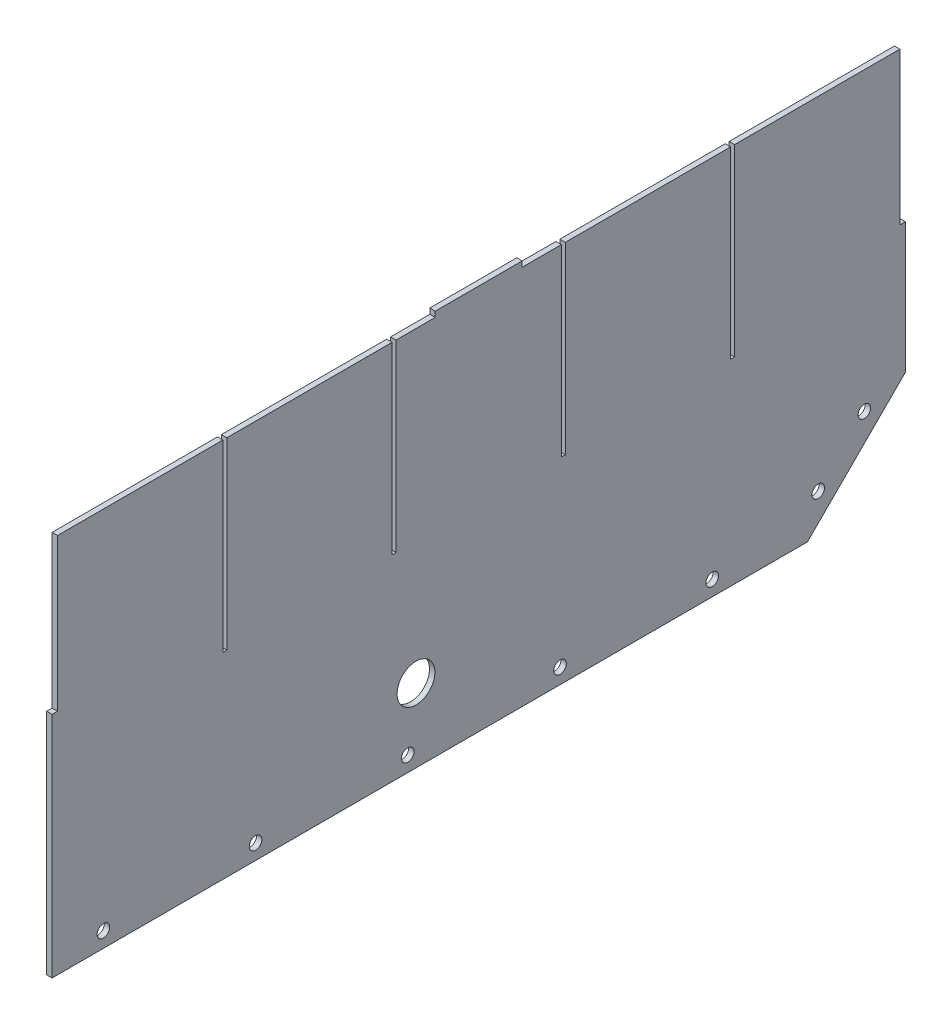
SolidWorks part; units mm, degrees
material "6061-T6 (SS)"
ref_plane "X-Y Datum" through (0, 0, 0) normal (0, 0, 1) x (1, 0, 0)
ref_plane "X-Z Datum" through (0, 0, 0) normal (0, 1, 0) x (1, 0, 0)
ref_plane "Y-Z Datum" through (0, 0, 0) normal (1, 0, 0) x (0, 0, -1)
sketch "Sketch1" plane through (0, 0, 0) normal (1, 0, 0) x (0, 0, -1)
  line L1 (-249.174, 82.55) -> (249.174, 82.55)
  line L2 (-249.174, 82.55) -> (-249.174, -82.55)
  line L3 (-249.174, -82.55) -> (249.174, -82.55)
  line L4 (249.174, 82.55) -> (249.174, -82.55)
  line L5 (-249.174, 82.55) -> (249.174, -82.55) construction
  line L6 (-249.174, -82.55) -> (249.174, 82.55) construction
  point P0 (0, 0)
  dimension "D1" = 165.1
  dimension "D2" = 498.348
extrude "Boss-Extrude1" add sketch "Sketch1" along normal mid plane 3.175
sketch "Sketch2" plane through (1.5875, 0, 0) normal (1, 0, 0) x (0, 0, -1)
  line L2 (249.174, -82.55) -> (192.024, -139.7)
  line L5 (-249.174, -82.55) -> (249.174, -82.55) construction
  line L6 (-249.174, -82.55) -> (249.174, -82.55)
  line L8 (192.024, -139.7) -> (-249.174, -139.7)
  line L9 (-249.174, -139.7) -> (-249.174, -82.55)
  line L11 (-249.174, 82.55) -> (-249.174, -82.55) construction
  line L12 (249.174, -82.55) -> (249.174, 82.55) construction
  line M10 (-249.174, -82.55) -> (249.174, -82.55)
  dimension "D1" = 45
  dimension "D5" = 57.15
extrude "Boss-Extrude2" add sketch "Sketch2" against normal blind 3.175 contours L2 M10 region at (1.5875, -110.5456, 13.9978)
sketch "Sketch3" plane through (-1.5875, 0, 0) normal (-1, 0, 0) x (0, 0, 1)
  line L0 (219.202, -139.7) -> (219.202, -130.81)
  line L1 (-192.024, -139.7) -> (249.174, -139.7) construction
  line L2 (219.202, -130.81) -> (249.174, -130.81)
  line L3 (249.174, 82.55) -> (249.174, -139.7) construction
  circle A0 centre (219.202, -130.81) radius 3.675
  dimension "D1" = 7.35
extrude "Cut-Extrude1" cut sketch "Sketch3" against normal through all contours L0 A0 L2 | L2 A0 L0 region at (-1.5875, -130.2901, 218.6821) region at (-1.5875, -132.3697, 220.7617)
pattern_linear "LPattern1" count 5 spacing 88.9 along (0, 0, -1) of "Cut-Extrude1"
sketch "Sketch4" plane through (-1.5875, 0, 0) normal (-1, 0, 0) x (0, 0, 1)
  line L0 (-206.3924, -125.3316) -> (-198.3102, -117.2494)
  line L1 (-249.174, -82.55) -> (-192.024, -139.7) construction
  line L2 (-192.024, -139.7) -> (-183.9418, -131.6178)
  line L3 (-183.9418, -131.6178) -> (-198.3102, -117.2494)
  circle A0 centre (-198.3102, -117.2494) radius 3.675
extrude "Cut-Extrude2" cut sketch "Sketch4" against normal through all and the other way through all contours L3 A0 L0 | L0 A0 L3 region at (-1.5875, -116.5141, -198.3102) region at (-1.5875, -119.4551, -198.3102)
pattern_linear "LPattern2" count 2 spacing 38.1 along (0, 0.7071, -0.7071) of "Cut-Extrude2"
sketch "Sketch5" plane through (1.5875, 0, 0) normal (1, 0, 0) x (0, 0, -1)
  line L1 (249.174, 82.55) -> (245.999, 82.55)
  line L2 (249.174, 82.55) -> (249.174, -6.35)
  line L3 (249.174, -6.35) -> (245.999, -6.35)
  line L4 (245.999, 82.55) -> (245.999, -6.35)
  line L5 (-249.174, 82.55) -> (-245.999, 82.55)
  line L6 (-249.174, 82.55) -> (-249.174, -6.35)
  line L7 (-249.174, -6.35) -> (-245.999, -6.35)
  line L8 (-245.999, 82.55) -> (-245.999, -6.35)
  dimension "D1" = 3.175
  dimension "D2" = 88.9
  dimension "D3" = 3.175
  dimension "D4" = 88.9
extrude "Cut-Extrude3" cut sketch "Sketch5" against normal through all
sketch "Sketch6" plane through (1.5875, 0, 0) normal (1, 0, 0) x (0, 0, -1)
  line L0 (122.174, 82.55) -> (249.174, 82.55) construction
  line L1 (149.4282, -24.892) -> (149.4282, 82.55) construction
  line L2 (122.174, 82.55) -> (249.174, 82.55)
  line L3 (149.4282, -24.892) -> (149.4282, 82.55)
  line L5 (149.4282, 82.55) -> (147.1422, 82.55)
  line L6 (149.4282, 82.55) -> (149.4282, -24.892)
  line L7 (149.4282, -24.892) -> (147.1422, -24.892)
  line L8 (147.1422, 82.55) -> (147.1422, -24.892)
  dimension "D1" = 2.286
  dimension "D2" = 107.442
extrude "Cut-Extrude4" cut sketch "Sketch6" against normal through all contours L2 L8 L7 L3 region at (1.5875, 28.829, -148.2852)
pattern_linear "LPattern3" count 4 spacing 98.8568 along (0, 0, 1) of "Cut-Extrude4"
sketch "Sketch8" plane through (1.5875, 0, 0) normal (1, 0, 0) x (0, 0, -1)
  line L0 (122.174, 85.725) -> (25.4, 85.725) construction
  line L1 (25.4, 82.55) -> (-25.4, 82.55)
  line L2 (25.4, 82.55) -> (25.4, 85.725)
  line L3 (25.4, 85.725) -> (-25.4, 85.725)
  line L4 (-25.4, 82.55) -> (-25.4, 85.725)
  line L5 (25.4, 82.55) -> (-25.4, 85.725) construction
  line L6 (25.4, 85.725) -> (-25.4, 82.55) construction
  point P0 (0, 84.1375)
  point P7 (0, 0)
  point P9 (0, 84.1375)
  dimension "D1" = 3.175
  dimension "D2" = 50.8
extrude "Boss-Extrude3" add sketch "Sketch8" against normal blind 3.175
sketch "Sketch9" plane through (1.5875, 0, 0) normal (1, 0, 0) x (0, 0, -1)
  line L0 (-249.174, -6.35) -> (-249.174, -139.7) construction
  line L1 (192.024, -139.7) -> (-249.174, -139.7) construction
  circle A0 centre (-36.6268, -96.7994) radius 11.05
  dimension "D3" = 22.1
  dimension "D1" = 212.5472
  dimension "D2" = 42.9006
extrude "Cut-Extrude5" cut sketch "Sketch9" against normal through all
